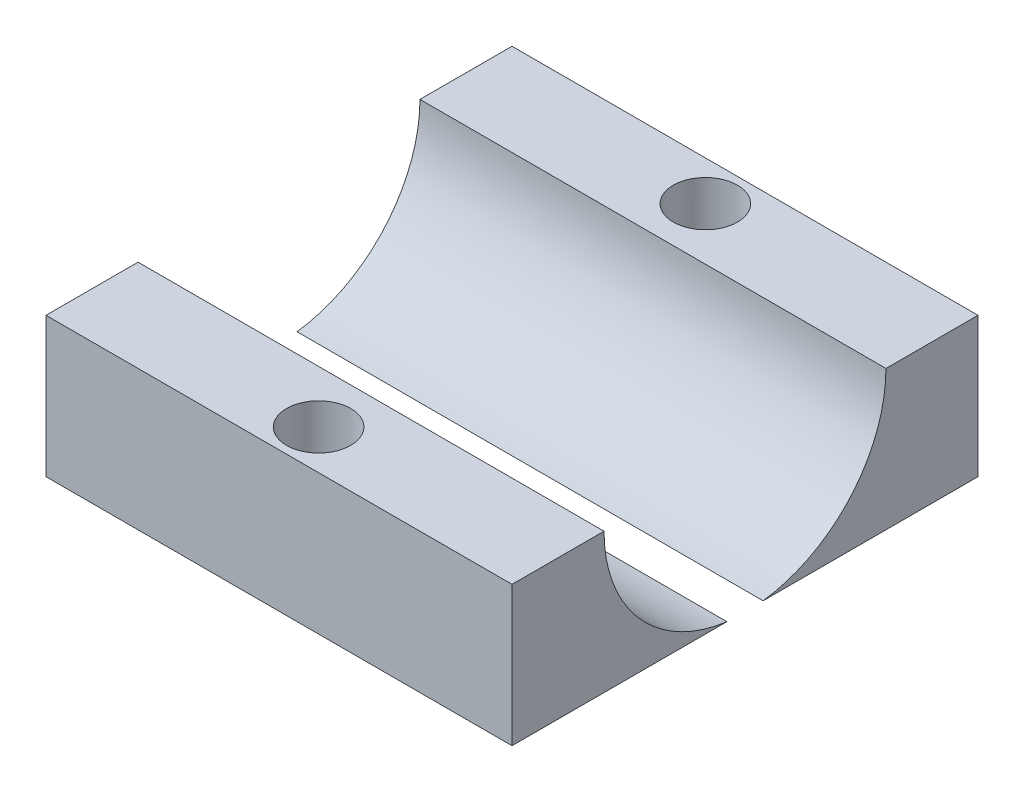
SolidWorks part; units mm, degrees
ref_plane "Front Plane" through (0, 0, 0) normal (0, 0, 1) x (1, 0, 0)
ref_plane "Top Plane" through (0, 0, 0) normal (0, 1, 0) x (1, 0, 0)
ref_plane "Right Plane" through (0, 0, 0) normal (1, 0, 0) x (0, 0, -1)
sketch "Sketch1" plane through (0, 0, 0) normal (1, 0, 0) x (0, 0, -1)
  line L0 (-20, -24) -> (20, -24)
  line L1 (20, -24) -> (20, -12)
  line L2 (20, -12) -> (-20, -12)
  line L3 (-20, -12) -> (-20, -24)
extrude "Clamp Lower Half" add sketch "Sketch1" along normal mid plane 40
sketch "Sketch2" plane through (0, 0, 0) normal (1, 0, 0) x (0, 0, -1)
  circle A0 centre (0, -12) radius 12.1
extrude "Handlebar Bore" cut sketch "Sketch2" against normal through all and the other way through all
sketch "Sketch3" plane through (0, 0, 0) normal (0, 1, 0) x (1, 0, 0)
  circle A0 centre (0, -16.6) radius 2.75
  circle A1 centre (0, 16.6) radius 2.75
extrude "M5 Clearance Holes" cut sketch "Sketch3" against normal through all and the other way through all
equation "\"BrW\" = 56.0"
equation "\"BrL\" = 80.0"
equation "\"BrH\" = 18.0"
equation "\"RailW\" = 30.0"
equation "\"RailW2\" = 38.0"
equation "\"RailH\" = 6.0"
equation "\"Slide\" = 0.3"
equation "\"StopT\" = 6.0"
equation "\"TubeD\" = 22.2"
equation "\"Liner\" = 1.0"
equation "\"ClampW\" = 40.0"
equation "\"ClampZ\" = 20.0"
equation "\"ClampY\" = -12.0"
equation "\"CapT\" = 12.0"
equation "\"BoltZ\" = 16.6"
equation "\"InsertD\" = 6.4"
equation "\"InsertL\" = 10.0"
equation "\"BoltD\" = 5.5"
equation "\"LockY\" = 15.0"
equation "\"LockD\" = 3.3"
